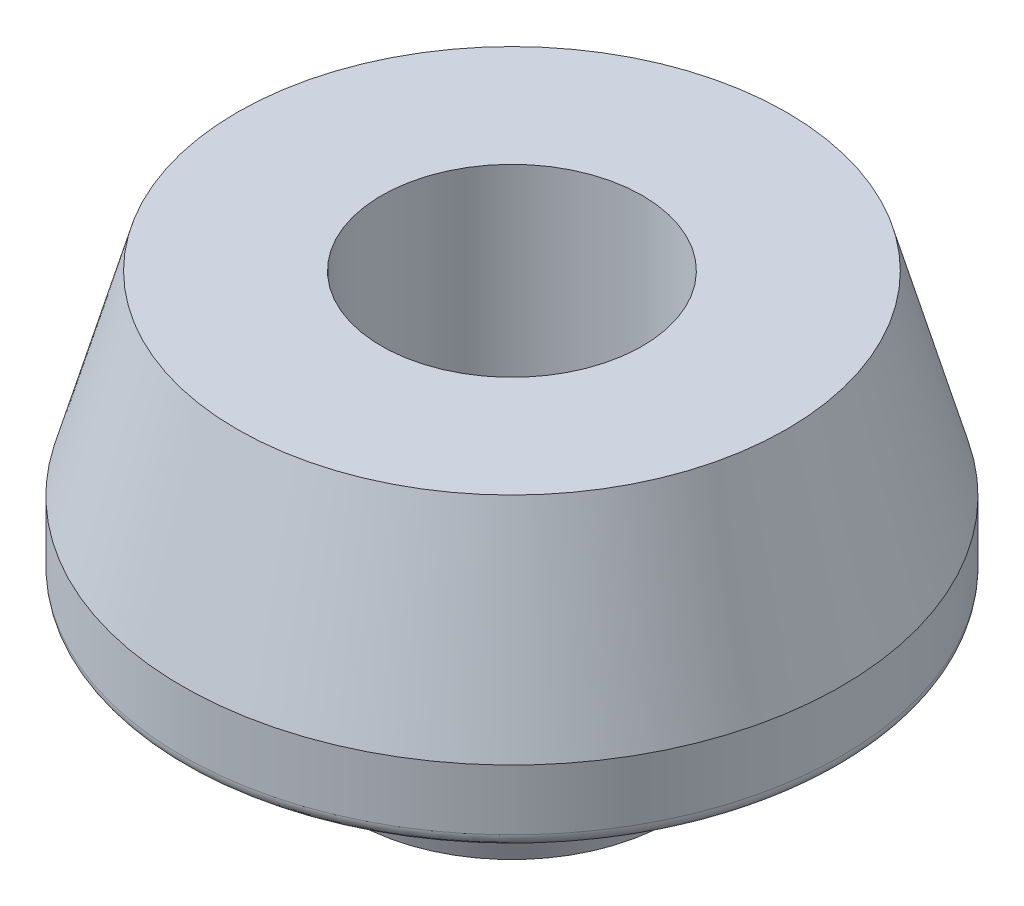
SolidWorks part; units mm, degrees
material "6061 Alloy"
ref_plane "Front Plane" through (0, 0, 0) normal (0, 0, 1) x (1, 0, 0)
ref_plane "Top Plane" through (0, 0, 0) normal (0, 1, 0) x (1, 0, 0)
ref_plane "Right Plane" through (0, 0, 0) normal (1, 0, 0) x (0, 0, -1)
sketch "Sketch1" plane through (0, 0, 0) normal (0, 0, 1) x (1, 0, 0)
  line L0 (0, -14.5) -> (0, 0) construction
  line L1 (0, 0) -> (10, 0) construction
  line L2 (10, 0) -> (4.75, 0)
  line L3 (4.75, 0) -> (4.75, -14.5)
  line L4 (4.75, -14.5) -> (5.75, -14.5)
  line L5 (5.75, -14.5) -> (7, -9.8)
  line L6 (7, -9.8) -> (12, -9.8)
  line L7 (12, -9.8) -> (12, -7.1)
  line L8 (12, -7.1) -> (10, 0)
  dimension "D1" = 14.5
  dimension "D2" = 10
  dimension "D3" = 5.25
  dimension "D4" = 9.8
  dimension "D5" = 1
  dimension "D6" = 5
  dimension "D7" = 2.7
  dimension "D8" = 12
revolve "Revolve1" add sketch "Sketch1" angle 360 about L0
fillet "Fillet1" radius 0.5 1 edges at (0, -9.8, -12)
